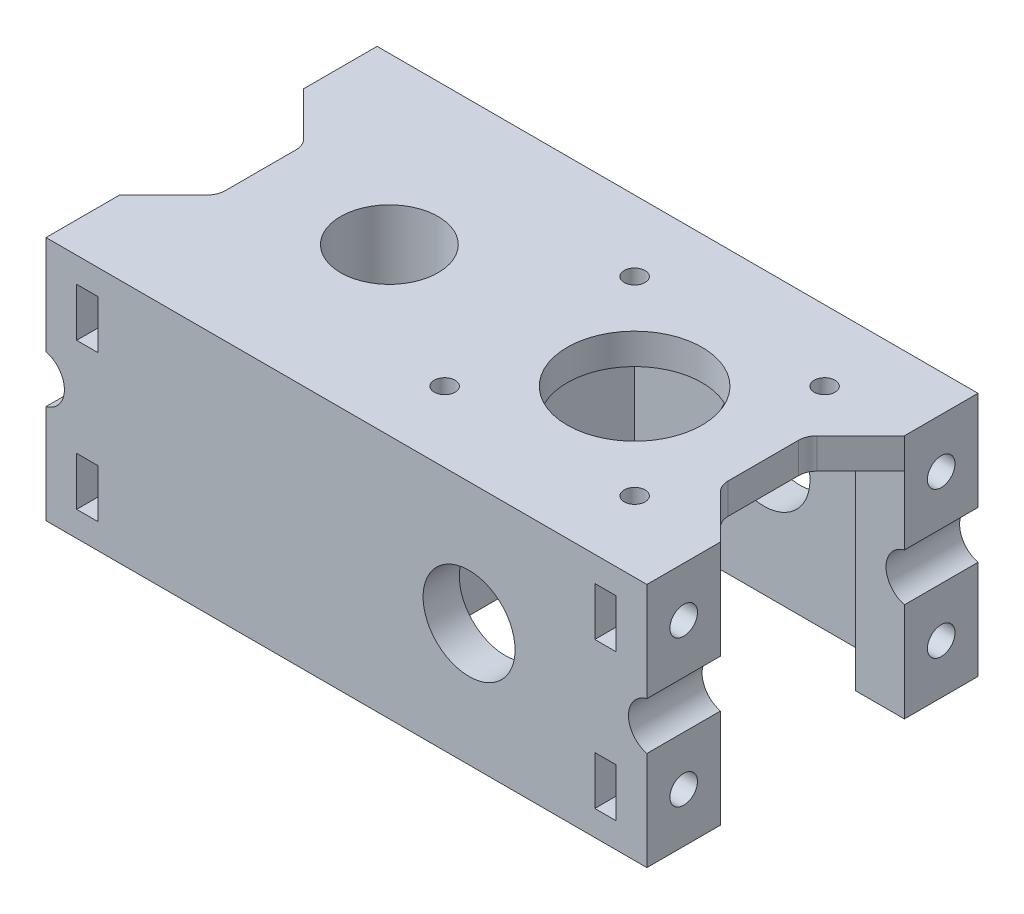
SolidWorks part; units mm, degrees
material "6061-T6 (SS)"
ref_plane "Front Plane" through (0, 0, 0) normal (0, 0, 1) x (1, 0, 0)
ref_plane "Top Plane" through (0, 0, 0) normal (0, 1, 0) x (1, 0, 0)
ref_plane "Right Plane" through (0, 0, 0) normal (1, 0, 0) x (0, 0, -1)
sketch "Sketch2" plane through (0, 0, 0) normal (0, 1, 0) x (1, 0, 0)
  line L0 (0, 0) -> (-40, 0) construction
  circle A0 centre (-40, 0) radius 6.35
  point P4 (-20, 0)
  line B0 (21.9075, 21.9075) -> (-21.9075, 21.9075) construction
  line B1 (21.9075, 21.9075) -> (21.9075, -21.9075) construction
  line B2 (21.9075, -21.9075) -> (-21.9075, -21.9075) construction
  line B3 (-21.9075, 21.9075) -> (-21.9075, -21.9075) construction
  line B4 (21.9075, 21.9075) -> (-21.9075, -21.9075) construction
  line B5 (21.9075, -21.9075) -> (-21.9075, 21.9075) construction
  circle B6 centre (0, 0) radius 21.9075 construction
  circle B7 centre (0, 0) radius 11 construction
  dimension "D2" = 12.7
  dimension "Rod Screw Separation" = 40
sketch_block_instance "Nema-17A-1"
sketch_block "Nema-17A" parameters "D2"=22, "D1"=43.815
sketch "Sketch3" plane through (0, 0, 0) normal (0, 1, 0) x (1, 0, 0)
  line L0 (0, 0) -> (21, 0) construction
  line L1 (21, 27) -> (-61, 27)
  line L2 (21, 27) -> (21, -27)
  line L3 (21, -27) -> (-61, -27)
  line L4 (-61, 27) -> (-61, -27)
  line L5 (-20, 27) -> (-20, -27) construction
  dimension "D1" = 82
  dimension "D2" = 21
  dimension "D3" = 21
  dimension "Width" = 54
extrude "Boss-Extrude2" add sketch "Sketch3" along normal mid plane 40
sketch "Sketch6" plane through (0, 20, 0) normal (0, 1, 0) x (1, 0, 0)
  line L0 (21.9075, 21.9075) -> (-21.9075, 21.9075) construction
  line L1 (21.9075, 21.9075) -> (-21.9075, 21.9075) construction
  line L2 (-21.9075, 21.9075) -> (-21.9075, -21.9075) construction
  line L3 (21.9075, 21.9075) -> (21.9075, -21.9075) construction
  line L4 (21.9075, -21.9075) -> (-21.9075, -21.9075) construction
  line L5 (-21.9075, 21.9075) -> (-21.9075, -21.9075) construction
  line L6 (21.9075, 21.9075) -> (21.9075, -21.9075) construction
  line L7 (21.9075, -21.9075) -> (-21.9075, -21.9075) construction
  line L8 (-21.1, 21.1) -> (-21.1, -21.1)
  line L9 (21.1, -21.1) -> (-21.1, -21.1)
  line L10 (21.1, 21.1) -> (21.1, -21.1)
  line L11 (21.1, 21.1) -> (-21.1, 21.1)
  dimension "D2" = 42.2
  dimension "D1" = 0.8075
extrude "Motor Pocket" cut sketch "Sketch6" against normal through all from offset 5
fillet "Fillet9" [suppressed] radius 3.175
sketch "Sketch7" plane through (0, 20, 0) normal (0, 1, 0) x (1, 0, 0)
  circle A0 centre (0, 0) radius 11
  dimension "D1" = 22
extrude "Motor Pilot Hole" cut sketch "Sketch7" against normal through all
hole_wizard "M3 Clearance Hole1 - Motor Mounting" positions "Sketch9" profile "Sketch10" hole size "M3" standard "Ansi Metric" end condition up to next
sketch "Sketch9" plane through (0, 20, 0) normal (0, 1, 0) x (-1, 0, 0)
  point P0 (15.4909, 15.4909)
  point P1 (-15.4909, -15.4909)
  point P3 (15.4909, -15.4909)
  point P5 (-15.4909, 15.4909)
sketch "Sketch10" plane through (-15.4909, 20, 15.4909) normal (1, 0, 0) x (0, 0, 1)
  line L0 (0, 0) -> (0, 5)
  line L1 (0, 5) -> (1.7, 5)
  line L2 (1.7, 5) -> (1.7, 0)
  line L5 (1.7, 0) -> (0, 0)
  line L11 (0, -6.35) -> (0, 107.95) construction
  dimension "Thru Hole Dia." = 3.4
  dimension "Thru Hole Depth" = 5
sketch "Sketch11" plane through (0, 20, 0) normal (0, 1, 0) x (1, 0, 0)
  circle A2 centre (-40, 0) radius 7.35
  circle A3 centre (-40, 0) radius 7.35
  dimension "D1" = 1
sketch "Sketch12" plane through (0, 20, 0) normal (0, 1, 0) x (1, 0, 0)
  circle A0 centre (-40, 0) radius 7.95
  dimension "D1" = 15.9
extrude "Cut-Extrude4" cut sketch "Sketch12" against normal through all
sketch "Sketch13" plane through (21, 0, 0) normal (1, 0, 0) x (0, 0, -1)
  line L0 (-27, -20) -> (-21.1, -20) construction
  line L1 (-9, -20) -> (9, -20)
  line L2 (-9, -20) -> (-9, -6)
  line L3 (-9, -6) -> (9, -6)
  line L4 (9, -20) -> (9, -6)
  line L5 (0, 0) -> (0, -6) construction
  line L6 (6.35, 0) -> (-6.35, 0) construction
  dimension "D1" = 18
  dimension "D2" = 14
extrude "Motor Plug Window" [suppressed] cut sketch "Sketch13" against normal up to next
sketch "Sketch14" plane through (0, -20, 0) normal (0, -1, 0) x (1, 0, 0)
  circle A0 centre (-40, 0) radius 11.1
  dimension "D1" = 22.2
extrude "Sleeve Bearing Recess" cut sketch "Sketch14" against normal blind 3.5
sketch "Sketch15" plane through (0, 0, 27) normal (0, 0, 1) x (1, 0, 0)
  circle A0 centre (0, 0) radius 7.5
  dimension "D1" = 15
extrude "Cut-Extrude7" cut sketch "Sketch15" against normal through all
ref_plane "Mid Plane" through (-20, 0, 0) normal (1, 0, 0) x (0, 0, -1)
sketch "Sketch16" plane through (0, 0, 0) normal (0, 0, 1) x (1, 0, 0)
  line L0 (21, 20) -> (21, -20) construction
  line L1 (21, 20) -> (21, -20)
  line L2 (21, 20) -> (29, 20)
  line L3 (29, 20) -> (29, 3.873)
  line L4 (29, -3.873) -> (29, -20)
  line L5 (29, -20) -> (21, -20)
  line L6 (0, 0) -> (30, 0) construction
  line L7 (-61, -20) -> (21, -20) construction
  line L8 (-20, -20) -> (-20, 20) construction
  line L9 (-20, -22) -> (-20, 22) construction
  line L10 (-61, 20) -> (21, 20) construction
  line L11 (-69, -20) -> (-61, -20)
  line L12 (-69, -3.873) -> (-69, -20)
  line L13 (-69, 20) -> (-69, 3.873)
  line L14 (-61, 20) -> (-69, 20)
  line L15 (-61, 20) -> (-61, -20)
  arc A0 (29, 3.873) -> (29, -3.873) centre (30, 0) ccw
  arc A1 (-69, 3.873) -> (-69, -3.873) centre (-70, 0) cw
  dimension "D2" = 1
  dimension "D4" = 8
  dimension "D1" = 16.127
  dimension "D3" = 90
  dimension "D5" = 8
extrude "Boss-Extrude8" add sketch "Sketch16" against normal blind 12 from offset 27 contours L3 A0 L4 L5 L1 L2
mirror "Mirror5" about plane through (0, 0, 0) normal (0, 0, 1) of "Boss-Extrude8"
mirror "Mirror6" about plane through (-20, 0, 0) normal (1, 0, 0) of "Mirror5", "Boss-Extrude8"
sketch "Sketch17" plane through (29, 0, 0) normal (1, 0, 0) x (0, 0, -1)
  line L0 (-21, 11.9365) -> (-21, -11.9365) construction
  line L1 (-21, 0) -> (0, 0) construction
  line L2 (-15, 20) -> (-27, 3.873) construction
  line L3 (-15, 20) -> (-27, 20) construction
  line L4 (-27, 20) -> (-27, 3.873) construction
  line L5 (-15, 3.873) -> (-27, 3.873) construction
  line L6 (-21, -7.9816) -> (-27, -7.9816)
  line L7 (-15, 20) -> (-15, 15) construction
  line L8 (-27, 20) -> (-27, 3.873) construction
  line L9 (-24.425, 13.9139) -> (-24.425, 9.9591) construction
  line L10 (-24.425, 9.9591) -> (-21, 7.9816) construction
  line L11 (-21, 7.9816) -> (-17.575, 9.9591)
  line L12 (-17.575, 9.9591) -> (-17.575, 13.9139)
  line L13 (-17.575, 13.9139) -> (-21, 15.8913)
  line L14 (-21, 15.8913) -> (-24.425, 13.9139) construction
  line L15 (-24.425, -9.9591) -> (-24.425, -13.9139) construction
  line L16 (-24.425, -13.9139) -> (-21, -15.8913) construction
  line L17 (-21, -15.8913) -> (-17.575, -13.9139)
  line L18 (-17.575, -13.9139) -> (-17.575, -9.9591)
  line L19 (-17.575, -9.9591) -> (-21, -7.9816)
  line L20 (-21, -7.9816) -> (-24.425, -9.9591) construction
  line L21 (-15, 20) -> (-15, 3.873) construction
  line L22 (-27, -3.873) -> (-27, -20) construction
  line L23 (-27, -7.9816) -> (-27, -15.8913)
  line L24 (-21, -15.8913) -> (-27, -15.8913)
  line L25 (-21, 15.8913) -> (-27, 15.8913)
  line L26 (-21, 7.9816) -> (-27, 7.9816)
  line L27 (-27, 15.8913) -> (-27, 7.9816)
  circle A0 centre (-21, 11.9365) radius 3.425 construction
  circle A1 centre (-21, -11.9365) radius 3.425 construction
  dimension "D1" = 6.85
  dimension "D2" = 6
  dimension "D3" = 6
hole_wizard "M4 Clearance Hole1" positions "Sketch19" profile "Sketch18" hole size "M4" standard "Ansi Metric"
sketch "Sketch19" plane through (29, 0, 0) normal (1, 0, 0) x (0, 0, -1)
  point P0 (-21, 11.9365)
  point P1 (-21, -11.9365)
sketch "Sketch18" plane through (29, 11.9365, 21) normal (0, 1, 0) x (0, 0, -1)
  line L0 (0, 0) -> (0, 13.3519)
  line L1 (0, 13.3519) -> (2.25, 12)
  line L2 (2.25, 12) -> (2.25, 0)
  line L5 (2.25, 0) -> (0, 0)
  line L10 (0, 13.3519) -> (-2.25, 12) construction
  line L11 (0, -6.35) -> (0, 107.95) construction
  dimension "Hole Dia." = 4.5
  dimension "Hole Depth" = 12
  dimension "Drill Angle" = 118
extrude "Clamp Nut Pockets" cut sketch "Sketch17" against normal blind 3.5 from offset 5
mirror "Mirror7" about plane through (0, 0, 0) normal (0, 0, 1) of "Clamp Nut Pockets", "M4 Clearance Hole1"
mirror "Mirror8" about plane through (-20, 0, 0) normal (1, 0, 0) of "Mirror7", "M4 Clearance Hole1", "Clamp Nut Pockets"
chamfer "Chamfer3" distance 8 angle 45 4 edges at (-61, 0, 15) (21, 17.5, -15)
fillet "Fillet8" radius 3 4 edges at (-61, 0, -7) (-61, 0, 7) (21, 17.5, 7) (21, 17.5, -7)
hole_wizard "M4x0.7 Tapped Hole1" [suppressed] positions "Sketch21" profile "Sketch20" tap size "M4x0.7" standard "Ansi Metric"
sketch "Sketch21" plane through (29, 0, 0) normal (1, 0, 0) x (0, 0, -1)
  line L0 (-21, 11.9365) -> (-21, -11.9365) construction
  point P0 (-21, -11.9365)
  point P1 (-21, 11.9365)
sketch "Sketch20" plane through (29, -11.9365, 21) normal (0, 1, 0) x (0, 0, -1)
  line L0 (0, 0) -> (0, 12.9914)
  line L1 (0, 12.9914) -> (1.65, 12)
  line L2 (1.65, 12) -> (1.65, 0)
  line L5 (1.65, 0) -> (0, 0)
  line L10 (0, 12.9914) -> (-1.65, 12) construction
  line L11 (0, -6.35) -> (0, 107.95) construction
  dimension "Tap Drill Dia." = 3.3
  dimension "Tap Drill Depth" = 12
  dimension "Drill Angle" = 118
mirror "Mirror9" [suppressed] about plane through (0, 0, 0) normal (0, 0, 1)
mirror "Mirror10" [suppressed] about plane through (-20, 0, 0) normal (1, 0, 0)
ref_plane "Center Plane" through (-20, 0, 0) normal (1, 0, 0) x (0, 0, -1)
fillet "Fillet10" [suppressed] radius 3.175
sketch "Sketch22" plane through (0, 15, 0) normal (0, -1, 0) x (1, 0, 0)
  line L0 (29, 15) -> (29, -15)
  line L1 (29, -15) -> (21, -15)
  line L2 (21, -15) -> (21, 15)
  line L3 (21, 15) -> (29, 15)
sketch "Sketch23" plane through (0, -20, 0) normal (0, -1, 0) x (1, 0, 0)
  circle A0 centre (-40, 0) radius 14.155
  dimension "D1" = 28.31
equation "\"Boss Offset@Boss-Extrude8\"=\"Width@Sketch3\"/2"
